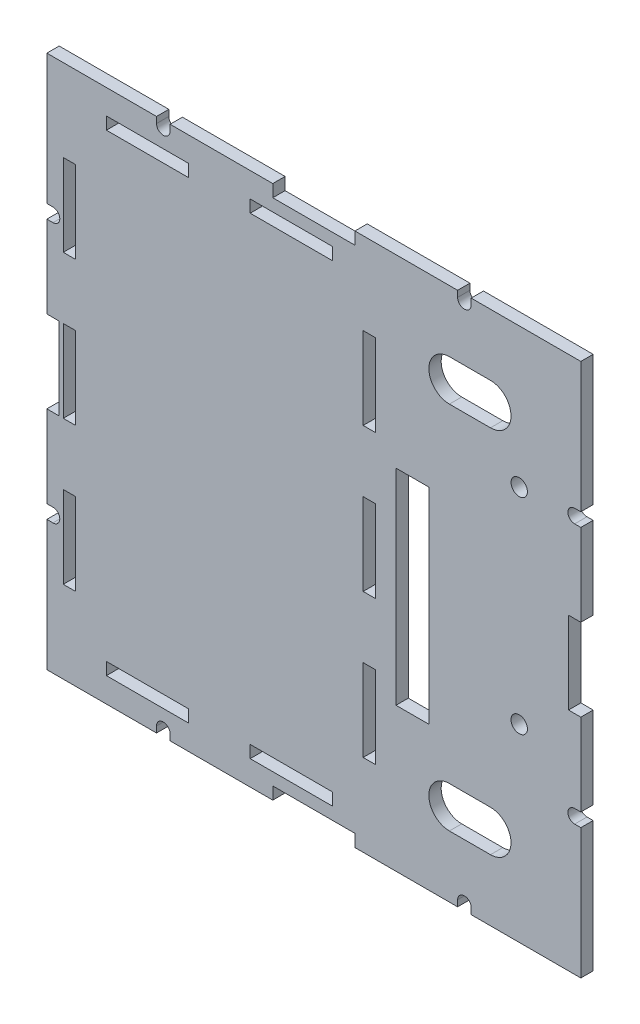
SolidWorks part; units mm, degrees
ref_plane "Front Plane" through (0, 0, 0) normal (0, 0, 1) x (1, 0, 0)
ref_plane "Top Plane" through (0, 0, 0) normal (0, 1, 0) x (1, 0, 0)
ref_plane "Right Plane" through (0, 0, 0) normal (1, 0, 0) x (0, 0, -1)
sketch "Sketch1" plane through (0, 0, 0) normal (0, 0, 1) x (1, 0, 0)
  line L0 (55, 0) -> (-55, 0) construction
  line L1 (65, -65) -> (-65, -65)
  line L2 (65, -65) -> (65, 65)
  line L3 (65, 65) -> (-65, 65)
  line L4 (-65, -65) -> (-65, 65)
  line L5 (65, -65) -> (-65, 65) construction
  line L6 (65, 65) -> (-65, -65) construction
  line L7 (10, 62) -> (-10, 62)
  line L8 (10, 62) -> (10, 65)
  line L9 (10, 65) -> (-10, 65)
  line L10 (-10, 62) -> (-10, 65)
  line L11 (10, 62) -> (-10, 65) construction
  line L12 (10, 65) -> (-10, 62) construction
  line L13 (-62, -10) -> (-65, -10)
  line L14 (-62, -10) -> (-62, 10)
  line L15 (-62, 10) -> (-65, 10)
  line L16 (-65, -10) -> (-65, 10)
  line L17 (-62, -10) -> (-65, 10) construction
  line L18 (-62, 10) -> (-65, -10) construction
  line L19 (10, -65) -> (-10, -65)
  line L20 (-10, -62) -> (-10, -65)
  line L21 (10, -62) -> (-10, -62)
  line L22 (10, -62) -> (10, -65)
  line L23 (0, -55) -> (0, 55) construction
  line L24 (62, 10) -> (65, 10)
  line L25 (65, -10) -> (65, 10)
  line L26 (62, -10) -> (65, -10)
  line L27 (62, -10) -> (62, 10)
  line L28 (-36.65, 63.5) -> (-36.65, 66.5) construction
  line L29 (-38.3, 63.5) -> (-38.3, 66.5)
  line L30 (-35, 63.5) -> (-35, 66.5)
  line L31 (-63.5, 31.65) -> (-66.5, 31.65) construction
  line L32 (-63.5, 30) -> (-66.5, 30)
  line L33 (-63.5, 33.3) -> (-66.5, 33.3)
  line L34 (36.65, 63.5) -> (36.65, 66.5) construction
  line L35 (38.3, 63.5) -> (38.3, 66.5)
  line L36 (35, 63.5) -> (35, 66.5)
  line L37 (63.5, 31.65) -> (66.5, 31.65) construction
  line L38 (63.5, 30) -> (66.5, 30)
  line L39 (63.5, 33.3) -> (66.5, 33.3)
  line L40 (63.5, -31.65) -> (66.5, -31.65) construction
  line L41 (63.5, -30) -> (66.5, -30)
  line L42 (63.5, -33.3) -> (66.5, -33.3)
  line L43 (36.65, -63.5) -> (36.65, -66.5) construction
  line L44 (38.3, -63.5) -> (38.3, -66.5)
  line L45 (35, -63.5) -> (35, -66.5)
  line L46 (-36.65, -63.5) -> (-36.65, -66.5) construction
  line L47 (-38.3, -63.5) -> (-38.3, -66.5)
  line L48 (-35, -63.5) -> (-35, -66.5)
  line L49 (-63.5, -31.65) -> (-66.5, -31.65) construction
  line L50 (-63.5, -30) -> (-66.5, -30)
  line L51 (-63.5, -33.3) -> (-66.5, -33.3)
  line L52 (-58, -45) -> (-61, -45)
  line L53 (-58, -10) -> (-61, -10)
  line L54 (-58, -10) -> (-58, 10)
  line L55 (-58, 10) -> (-61, 10)
  line L56 (-61, -10) -> (-61, 10)
  line L57 (-58, -10) -> (-61, 10) construction
  line L58 (-58, 10) -> (-61, -10) construction
  line L59 (-58, 25) -> (-61, 25)
  line L60 (-58, 25) -> (-58, 45)
  line L61 (-58, 45) -> (-61, 45)
  line L62 (-61, 25) -> (-61, 45)
  line L63 (-58, 25) -> (-61, 45) construction
  line L64 (-58, 45) -> (-61, 25) construction
  line L65 (-61, -25) -> (-61, -45)
  line L66 (-58, -25) -> (-61, -25)
  line L67 (-58, -25) -> (-58, -45)
  line L68 (-15.5, -59) -> (4.5, -59)
  line L69 (-30.5, 56) -> (-50.5, 56)
  line L70 (-30.5, 56) -> (-30.5, 59)
  line L71 (-30.5, 59) -> (-50.5, 59)
  line L72 (-50.5, 56) -> (-50.5, 59)
  line L73 (-30.5, 56) -> (-50.5, 59) construction
  line L74 (-30.5, 59) -> (-50.5, 56) construction
  line L75 (-15.5, 56) -> (4.5, 56)
  line L76 (-15.5, 56) -> (-15.5, 59)
  line L77 (-15.5, 59) -> (4.5, 59)
  line L78 (4.5, 56) -> (4.5, 59)
  line L79 (-15.5, 56) -> (4.5, 59) construction
  line L80 (-15.5, 59) -> (4.5, 56) construction
  line L81 (4.5, -56) -> (4.5, -59)
  line L82 (-15.5, -56) -> (4.5, -56)
  line L83 (-15.5, -56) -> (-15.5, -59)
  line L84 (-30.5, -59) -> (-50.5, -59)
  line L85 (-50.5, -56) -> (-50.5, -59)
  line L86 (-30.5, -56) -> (-50.5, -56)
  line L87 (-30.5, -56) -> (-30.5, -59)
  line L88 (43, -45) -> (33, -45) construction
  line L89 (12, 45) -> (15, 45)
  line L90 (12, 45) -> (12, 25)
  line L91 (12, 25) -> (15, 25)
  line L92 (15, 45) -> (15, 25)
  line L93 (12, 45) -> (15, 25) construction
  line L94 (12, 25) -> (15, 45) construction
  line L95 (15, -10) -> (12, -10)
  line L96 (15, -10) -> (15, 10)
  line L97 (15, 10) -> (12, 10)
  line L98 (12, -10) -> (12, 10)
  line L99 (15, -10) -> (12, 10) construction
  line L100 (15, 10) -> (12, -10) construction
  line L101 (12, -45) -> (15, -45)
  line L102 (12, -45) -> (12, -25)
  line L103 (12, -25) -> (15, -25)
  line L104 (15, -45) -> (15, -25)
  line L105 (12, -45) -> (15, -25) construction
  line L106 (12, -25) -> (15, -45) construction
  line L107 (28, -30) -> (20, -30)
  line L108 (28, -30) -> (28, 20)
  line L109 (28, 20) -> (20, 20)
  line L110 (20, -30) -> (20, 20)
  line L111 (28, -30) -> (20, 20) construction
  line L112 (28, 20) -> (20, -30) construction
  line L117 (43, 45) -> (33, 45) construction
  line L118 (43, 40) -> (33, 40)
  line L119 (43, 50) -> (33, 50)
  line L120 (43, -40) -> (33, -40)
  line L121 (43, -50) -> (33, -50)
  arc A0 (-38.3, 63.5) -> (-35, 63.5) centre (-36.65, 63.5) ccw
  arc A1 (-35, 66.5) -> (-38.3, 66.5) centre (-36.65, 66.5) ccw
  arc A2 (-63.5, 30) -> (-63.5, 33.3) centre (-63.5, 31.65) ccw
  arc A3 (-66.5, 33.3) -> (-66.5, 30) centre (-66.5, 31.65) ccw
  arc A4 (38.3, 63.5) -> (35, 63.5) centre (36.65, 63.5) cw
  arc A5 (35, 66.5) -> (38.3, 66.5) centre (36.65, 66.5) cw
  arc A6 (63.5, 30) -> (63.5, 33.3) centre (63.5, 31.65) cw
  arc A7 (66.5, 33.3) -> (66.5, 30) centre (66.5, 31.65) cw
  arc A8 (63.5, -30) -> (63.5, -33.3) centre (63.5, -31.65) ccw
  arc A9 (66.5, -33.3) -> (66.5, -30) centre (66.5, -31.65) ccw
  arc A10 (38.3, -63.5) -> (35, -63.5) centre (36.65, -63.5) ccw
  arc A11 (35, -66.5) -> (38.3, -66.5) centre (36.65, -66.5) ccw
  arc A12 (-38.3, -63.5) -> (-35, -63.5) centre (-36.65, -63.5) cw
  arc A13 (-35, -66.5) -> (-38.3, -66.5) centre (-36.65, -66.5) cw
  arc A14 (-63.5, -30) -> (-63.5, -33.3) centre (-63.5, -31.65) cw
  arc A15 (-66.5, -33.3) -> (-66.5, -30) centre (-66.5, -31.65) cw
  arc A20 (43, 40) -> (43, 50) centre (43, 45) ccw
  arc A21 (33, 50) -> (33, 40) centre (33, 45) ccw
  circle A22 centre (50, 31) radius 2
  circle A23 centre (50, -19) radius 2
  arc A24 (43, -40) -> (43, -50) centre (43, -45) cw
  arc A25 (33, -50) -> (33, -40) centre (33, -45) cw
  point P0 (0, 0)
  point P6 (0, 63.5)
  point P11 (-63.5, 0)
  point P16 (-36.65, 65)
  point P35 (-65, 31.65)
  point P42 (-59.5, 35)
  point P45 (36.65, 65)
  point P52 (65, 31.65)
  point P59 (65, -31.65)
  point P66 (36.65, -65)
  point P73 (-36.65, -65)
  point P80 (-65, -31.65)
  point P85 (-59.5, 0)
  point P94 (-5.5, 57.5)
  point P100 (-40.5, 57.5)
  point P108 (13.5, -35)
  point P117 (13.5, 35)
  point P123 (13.5, 0)
  point P132 (24, -5)
  point P138 (38, -45)
  point P143 (38, 45)
  dimension "D7" = 1.65
  dimension "D10" = 1.65
  dimension "D29" = 10
  dimension "D31" = 5
  dimension "D35" = 4
  dimension "D1" = 130
  dimension "D2" = 130
  dimension "D3" = 20
  dimension "D4" = 3
  dimension "D5" = 20
  dimension "D6" = 3
  dimension "D8" = 3
  dimension "D9" = 25
  dimension "D11" = 3
  dimension "D12" = 20
  dimension "D13" = 20
  dimension "D14" = 3
  dimension "D15" = 15
  dimension "D16" = 4
  dimension "D17" = 20
  dimension "D18" = 3
  dimension "D19" = 6
  dimension "D20" = 15
  dimension "D21" = 10.5
  dimension "D22" = 10.5
  dimension "D23" = 3
  dimension "D24" = 20
  dimension "D25" = 15
  dimension "D26" = 15
  dimension "D27" = 50
  dimension "D28" = 8
  dimension "5" = 35
  dimension "D30" = 37
  dimension "D32" = 15
  dimension "D33" = 27
  dimension "D36" = 31
  dimension "D37" = 50
  dimension "D38" = 50
extrude "Boss-Extrude1" add sketch "Sketch1" along normal blind 3 contours L26 L27 L24 L2 L3 L8 L7 L10 L4 L15 L14 L13 L1 L20 L21 L22 region at (-0.6989, 0.1216, 0)
